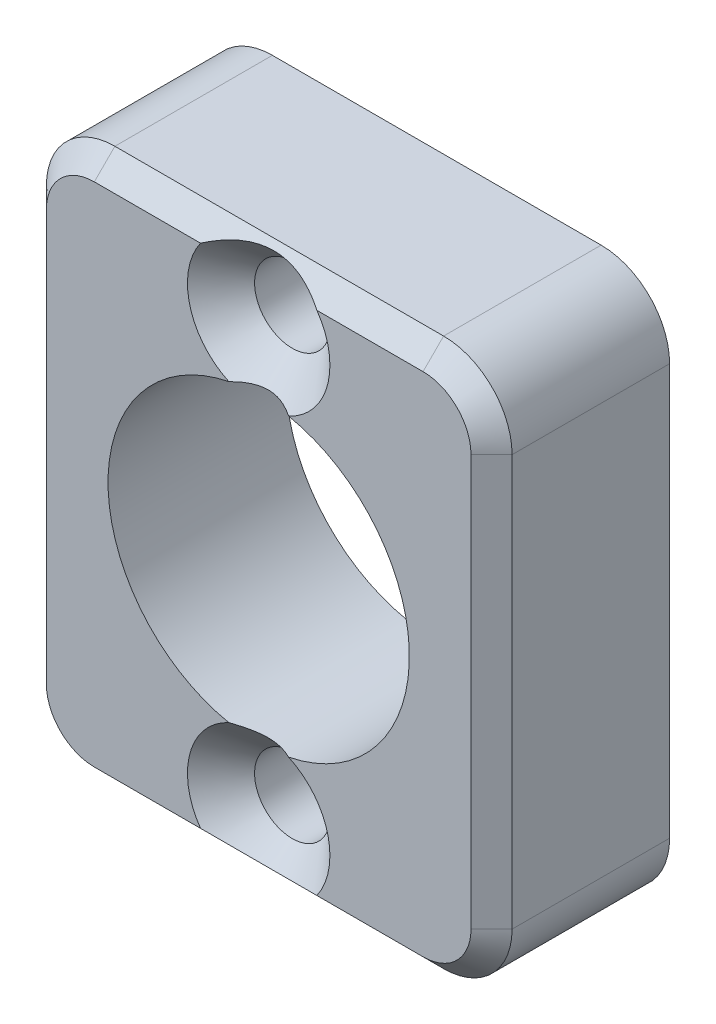
SolidWorks part; units mm, degrees
material "3.1355 (EN-AW 2024)"
ref_plane "Front" through (0, 0, 0) normal (0, 0, 1) x (1, 0, 0)
ref_plane "Top" through (0, 0, 0) normal (0, 1, 0) x (1, 0, 0)
ref_plane "Right" through (0, 0, 0) normal (1, 0, 0) x (0, 0, -1)
sketch "Эскиз1" plane through (0, 0, 0) normal (0, 0, 1) x (1, 0, 0)
  line L1 (-17, 20) -> (17, 20)
  line L2 (-17, 20) -> (-17, -20)
  line L3 (-17, -20) -> (17, -20)
  line L4 (17, 20) -> (17, -20)
  line L5 (-17, 20) -> (17, -20) construction
  line L6 (-17, -20) -> (17, 20) construction
  point P0 (0, 0)
  dimension "D1" = 34
  dimension "D2" = 40
extrude "База" add sketch "Эскиз1" against normal blind 13
sketch "Эскиз2" plane through (0, 0, -13) normal (0, 0, 1) x (1, 0, 0)
  circle A0 centre (0, 0) radius 11
  dimension "D1" = 22
extrude "ВырезПодшипника" cut sketch "Эскиз2" along normal blind 13
hole_wizard "КреплениеM6" positions "Эскиз6" profile "Эскиз5" countersink size "M5" standard "ISO" end condition through all
sketch "Эскиз6" plane through (0, 0, 0) normal (0, 0, 1) x (1, 0, 0)
  line L0 (0, 15.5) -> (0, 20) construction
  line L1 (17, 20) -> (-17, 20) construction
  line L4 (0, 15.5) -> (0, 11) construction
  line L7 (0, -15.5) -> (0, -11) construction
  line L10 (0, -15.5) -> (0, -20) construction
  line L11 (-17, -20) -> (17, -20) construction
  circle A0 centre (0, 0) radius 11 construction
  circle A2 centre (0, 0) radius 11 construction
  point P0 (0, 15.5)
  point P2 (0, -15.5)
sketch "Эскиз5" plane through (0, 15.5, 0) normal (1, 0, 0) x (0, -1, 0)
  line L0 (0, 0) -> (0, 13)
  line L1 (0, 13) -> (2.75, 13)
  line L2 (2.75, 13) -> (2.75, 2.45)
  line L3 (2.75, 2.45) -> (5.2, 0)
  line L5 (5.2, 0) -> (0, 0)
  line L6 (-2.75, 2.45) -> (-5.2, 0) construction
  line L11 (0, -6.35) -> (0, 107.95) construction
  dimension "Диаметр сквозного отверстия" = 5.5
  dimension "Глубина сквозного отверстия" = 13
  dimension "Диаметр передней зенковки" = 10.4
  dimension "Угол передней зенковки" = 90
fillet "Скругление" radius 5 4 edges at (-17, -20, -6.5) (17, -20, -6.5) (-17, 20, -6.5) (17, 20, -6.5)
chamfer "Фаска1" distance 1.5 angle 45 10 edges at (-15.5355, -18.5355, 0) (-7.3029, -20, 0) (7.3029, -20, 0) (15.5355, -18.5355, 0) (17, 0, 0) (15.5355, 18.5355, 0) (-7.3029, 20, 0) (7.3029, 20, 0) (-15.5355, 18.5355, 0) (-17, 0, 0)
